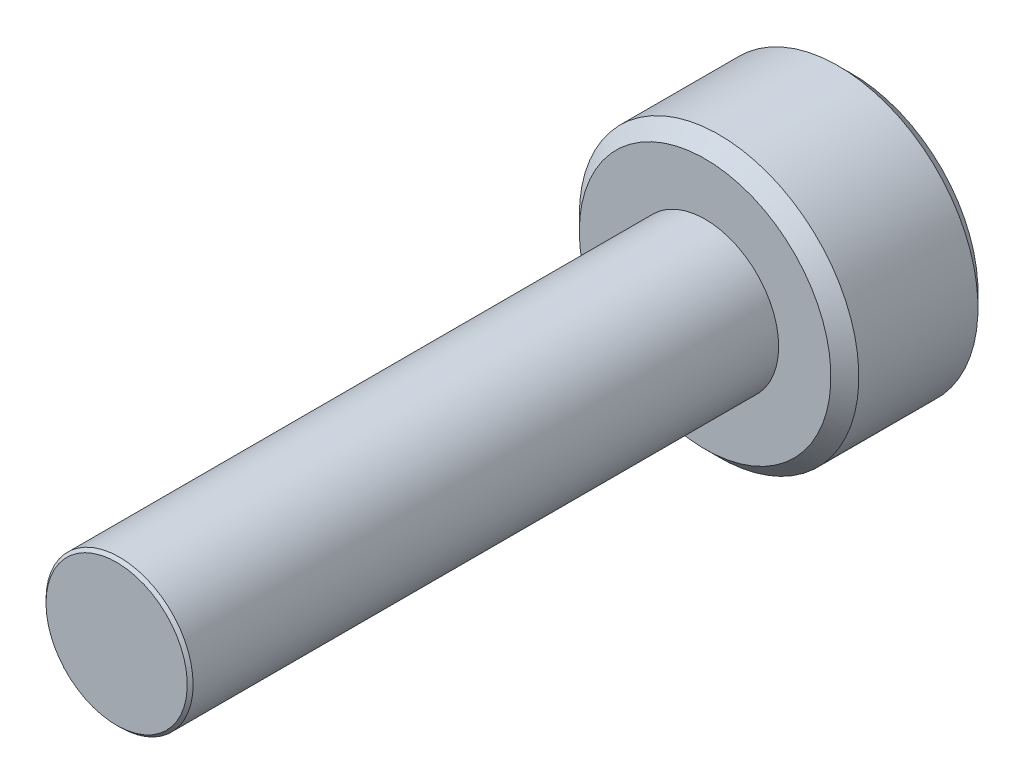
SolidWorks part; units mm, degrees
ref_plane "Front Plane" through (0, 0, 0) normal (0, 0, 1) x (1, 0, 0)
ref_plane "Top Plane" through (0, 0, 0) normal (0, 1, 0) x (1, 0, 0)
ref_plane "Right Plane" through (0, 0, 0) normal (1, 0, 0) x (0, 0, -1)
sketch "Sketch1" plane through (0, 0, 0) normal (0, 0, 1) x (1, 0, 0)
  circle A0 centre (0, 0) radius 1
  dimension "OD" = 2
extrude "Extrude1" add sketch "Sketch1" against normal blind 8
sketch "Sketch2" plane through (0, 0, 0) normal (0, 0, 1) x (1, 0, 0)
  circle A0 centre (0, 0) radius 1 construction
  circle A1 centre (0, 0) radius 1
curve "Helix/Spiral1" pitch 0.4 height 8.4 radius 1 centre (0, 0, 0) axis (0, 0, -1) start towards (0, 1, 0) parameters "pitch"=0.4
sketch "Sketch3" plane through (0, 0, 0) normal (1, 0, 0) x (0, 0, -1)
  line L0 (-0.35, 1) -> (-0.2, 0.7402)
  line L1 (-0.2, 0.7402) -> (-0.15, 0.7402)
  line L2 (-0.15, 0.7402) -> (0, 1)
  line L3 (-0.35, 1) -> (0, 1)
  line L4 (-0.175, 1) -> (-0.175, 0.7402) construction
  line L5 (-0.275, 0.8701) -> (-0.075, 0.8701) construction
  line L6 (0, 1) -> (0, -1) construction
  dimension "D1" = 0.05
  dimension "D2" = 0.2
  dimension "D3" = 60
sweep "Cut-Sweep1" cut profiles "Sketch3" path "Helix/Spiral1" align with end faces yes
sketch "Sketch4" plane through (0, 0, 0) normal (1, 0, 0) x (0, 0, -1)
  line L0 (0.3598, 1) -> (0, 0.4862)
  line L1 (0, 0.4862) -> (0, 1)
  line L2 (0.3598, 1) -> (0, 1)
  line L3 (-0.35, 1) -> (0, 1) construction
  line L4 (0, 0) -> (7.0209, 0) construction
  dimension "D1" = 55
  dimension "D2" = 0.254
revolve "Cut-Revolve1" cut sketch "Sketch4" angle 360 about L4
sketch "Sketch6" plane through (0, 0, -8) normal (0, 0, -1) x (-1, 0, 0)
  circle A0 centre (0, 0) radius 1.9
  dimension "head dia" = 3.8
extrude "Extrude2" add sketch "Sketch6" along normal blind 2
sketch "Sketch7" plane through (0, 0, -10) normal (0, 0, -1) x (-1, 0, 0)
  line L1 (0, 0.866) -> (-0.75, 0.433)
  line L2 (-0.75, 0.433) -> (-0.75, -0.433)
  line L3 (-0.75, -0.433) -> (0, -0.866)
  line L4 (0, -0.866) -> (0.75, -0.433)
  line L5 (0.75, -0.433) -> (0.75, 0.433)
  line L6 (0.75, 0.433) -> (0, 0.866)
  circle A0 centre (0, 0) radius 0.75 construction
  dimension "hex dia" = 1.5
extrude "Cut-Extrude1" cut sketch "Sketch7" against normal blind 1.125
sketch "Sketch8" plane through (0, 0, -10) normal (0, 0, -1) x (-1, 0, 0)
  circle A0 centre (0, 0) radius 0.866
extrude "Cut-Extrude2" cut sketch "Sketch8" against normal through all draft 45
chamfer "Chamfer1" distance 0.19 angle 45 2 edges at (-1.9, 0, -10) (-1.9, 0, -8)
sketch "Sketch10" plane through (0, 0, -8) normal (0, 0, 1) x (1, 0, 0)
  circle A1 centre (0, 0) radius 1
  circle A2 centre (0, 0) radius 1
  dimension "D1" = 0
ref_plane "Plane1" through (0, 0, 0) normal (0, 0, 1) x (1, 0, 0)
extrude "partial thread" add sketch "Sketch10" along normal up to surface (8 mm away) separate body up to plane "Plane1"
chamfer "Chamfer2" distance 0.04 angle 45 1 edges at (1, 0, 0)
combine bodies "Combine1" operation type add bodies to combine 107 108
sketch "Sketch9" plane through (0, 0, 0) normal (1, 0, 0) x (0, 0, -1)
  line L0 (0, 1) -> (0, -1) construction
  line L1 (1, 1) -> (1, -1) construction
  dimension "D1" = 1
equation "\"D3@Helix/Spiral1\" = \"screw length@Extrude1\"+\"pitch@Helix/Spiral1\""
equation "\"D1@Sketch3\" = \"pitch@Helix/Spiral1\"*.125"
equation "\"D2@Sketch3\" = \"pitch@Helix/Spiral1\"*.5"
equation "\"D1@Cut-Extrude1\" = \"hex dia@Sketch7\"*.75"
equation "\"D1@Chamfer1\" = \"head dia@Sketch6\"*.05"
equation "\"D1@Sketch9\" = \"pitch@Helix/Spiral1\"*2.5"
equation "\"D1@Chamfer2\"=\"OD@Sketch1\"*.02"
